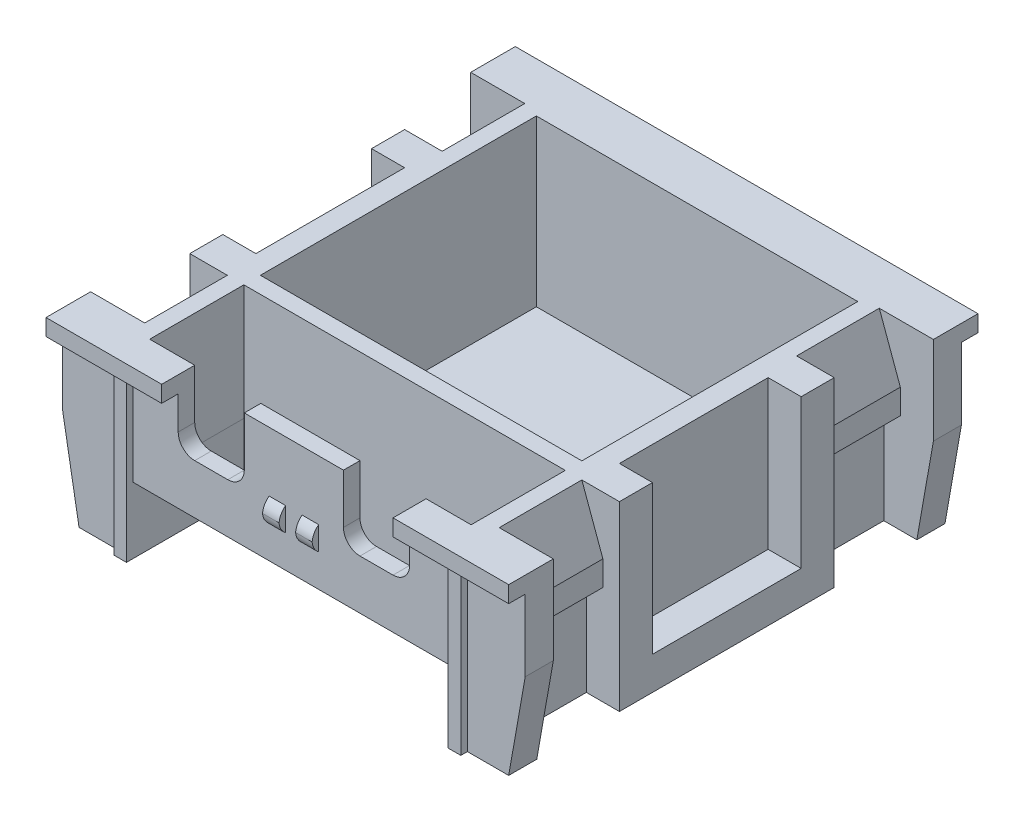
SolidWorks part; units mm, degrees
ref_plane "Front Plane" through (0, 0, 0) normal (0, 0, 1) x (1, 0, 0)
ref_plane "Top Plane" through (0, 0, 0) normal (0, 1, 0) x (1, 0, 0)
ref_plane "Right Plane" through (0, 0, 0) normal (1, 0, 0) x (0, 0, -1)
sketch "Sketch1" plane through (0, 0, 0) normal (0, 1, 0) x (1, 0, 0)
  line L1 (-14, 14.2) -> (0, 14.2)
  line L2 (-14, 14.2) -> (-14, 0)
  line L3 (-14, 0) -> (0, 0)
  line L4 (0, 14.2) -> (0, 0)
  dimension "D1" = 14.2
  dimension "D2" = 14
extrude "Boss-Extrude2" add sketch "Sketch1" against normal blind 5.5
sketch "Sketch2" plane through (0, 0, 0) normal (0, 1, 0) x (1, 0, 0)
  line L1 (-14, 12.85) -> (-13, 12.85)
  line L2 (-14, 12.85) -> (-14, 10.35)
  line L3 (-14, 10.35) -> (-13, 10.35)
  line L4 (-13, 12.85) -> (-13, 10.35)
  line L5 (-7, 14.6083) -> (-7, 0.4083)
  line L6 (0, 10.35) -> (-1, 10.35)
  line L7 (-1, 12.85) -> (-1, 10.35)
  line L8 (0, 12.85) -> (0, 10.35)
  line L9 (0, 12.85) -> (-1, 12.85)
  line L10 (0, 3.85) -> (0, 1.35)
  line L11 (-14, 3.85) -> (-13, 3.85)
  line L12 (-14, 3.85) -> (-14, 1.35)
  line L13 (-14, 1.35) -> (-13, 1.35)
  line L14 (-13, 3.85) -> (-13, 1.35)
  line L15 (0, 1.35) -> (-1, 1.35)
  line L16 (-1, 3.85) -> (-1, 1.35)
  line L17 (0, 3.85) -> (-1, 3.85)
  line L18 (-14, 14.2) -> (-14, 0) construction
  line L19 (0, 0) -> (0, 14.2) construction
  line L20 (0, 14.2) -> (-14, 14.2) construction
  line L21 (-14, 0) -> (0, 0) construction
  line M5 (-14, 14.2) -> (-14, 0)
  line M7 (0, 0) -> (0, 14.2)
  dimension "D1" = 0
  dimension "D2" = 0
  dimension "D3" = 1
  dimension "D4" = 1
  dimension "D5" = 0
  dimension "D6" = 1.35
  dimension "D7" = 1.35
  dimension "D8" = 2.5
  dimension "D9" = 2.5
extrude "Cut-Extrude1" cut sketch "Sketch2" against normal blind 2.5 contours L4 L1 L3 M5 | L9 L7 L6 M7 | L14 L11 L13 M5 | L17 L16 L15 M7 region at (-13.5, 0, -2.6) region at (-13.5, 0, -11.6) region at (-0.5, 0, -11.6) region at (-0.5, 0, -2.6)
sketch "Sketch3" plane through (0, -5.5, 0) normal (0, -1, 0) x (1, 0, 0)
  line L0 (-14, -1.35) -> (-12.5, -1.35)
  line L1 (-14, -1.35) -> (-14, -3.85)
  line L2 (-14, -3.85) -> (-12.5, -3.85)
  line L3 (-12.5, -1.35) -> (-12.5, -3.85)
  line L4 (-14, 0) -> (0, 0) construction
  line L5 (-1.5, -3.85) -> (0, -3.85)
  line L6 (0, -1.35) -> (0, -3.85)
  line L7 (-1.5, -1.35) -> (-1.5, -3.85)
  line L8 (-1.5, -1.35) -> (0, -1.35)
  line L9 (0, -10.35) -> (0, -12.85)
  line L10 (-14, -10.35) -> (-12.5, -10.35)
  line L11 (-14, -10.35) -> (-14, -12.85)
  line L12 (-14, -12.85) -> (-12.5, -12.85)
  line L13 (-12.5, -10.35) -> (-12.5, -12.85)
  line L14 (0, -12.85) -> (-1.5, -12.85)
  line L15 (-1.5, -10.35) -> (-1.5, -12.85)
  line L16 (0, -10.35) -> (-1.5, -10.35)
  line L17 (-14, -14.2) -> (-14, 0) construction
  line L18 (0, 0) -> (0, -14.2) construction
  line L19 (0, -14.2) -> (-14, -14.2) construction
  point P8 (-0.75, -12.85)
  dimension "D1" = 0
  dimension "D2" = 0
  dimension "D3" = 2.5
  dimension "D4" = 0
  dimension "D5" = 1.5
  dimension "D6" = 2.5
  dimension "D7" = 2.5
  dimension "D8" = 0
  dimension "D9" = 1.5
  dimension "D10" = 1.35
  dimension "D11" = 2.5
  dimension "D12" = 1.5
  dimension "D13" = 2.5
  dimension "D14" = 1.35
  dimension "D15" = 1.35
  dimension "D16" = 1.35
  dimension "D17" = 1.5
extrude "Cut-Extrude2" cut sketch "Sketch3" against normal blind 3
sketch "Sketch4" plane through (0, 0, 0) normal (0, 1, 0) x (1, 0, 0)
  line L0 (0, 3.85) -> (-1, 3.85) construction
  line L1 (0, 10.35) -> (-0.5, 10.35)
  line L2 (0, 10.35) -> (0, 3.85)
  line L3 (0, 3.85) -> (-0.5, 3.85)
  line L4 (-0.5, 10.35) -> (-0.5, 3.85)
  line L5 (-14, 10.35) -> (-13, 10.35) construction
  line L6 (-13.5, 10.35) -> (-14, 10.35)
  line L7 (-13.5, 10.35) -> (-13.5, 3.85)
  line L8 (-13.5, 3.85) -> (-14, 3.85)
  line L9 (-14, 10.35) -> (-14, 3.85)
extrude "Cut-Extrude3" cut sketch "Sketch4" against normal blind 5.5
sketch "Sketch5" plane through (0, 0, 0) normal (0, 1, 0) x (1, 0, 0)
  line L0 (-13.5, 3.85) -> (-13.5, 10.35) construction
  line L1 (-13.5, 9.35) -> (-12.5, 9.35)
  line L2 (-13.5, 9.35) -> (-13.5, 4.85)
  line L3 (-13.5, 4.85) -> (-12.5, 4.85)
  line L4 (-12.5, 9.35) -> (-12.5, 4.85)
  line L5 (-0.5, 10.35) -> (-0.5, 3.85) construction
  line L6 (-0.5, 9.35) -> (-1.5, 9.35)
  line L7 (-0.5, 9.35) -> (-0.5, 4.85)
  line L8 (-0.5, 4.85) -> (-1.5, 4.85)
  line L9 (-1.5, 9.35) -> (-1.5, 4.85)
  line L10 (-13.5, 10.35) -> (-13, 10.35) construction
  line L11 (-13.5, 3.85) -> (-13, 3.85) construction
  line L12 (-0.5, 10.35) -> (-1, 10.35) construction
  line L13 (-0.5, 3.85) -> (-1, 3.85) construction
  dimension "D1" = 1
  dimension "D2" = 1
  dimension "D3" = 1
  dimension "D4" = 1
  dimension "D5" = 1
  dimension "D6" = 1
extrude "Cut-Extrude4" cut sketch "Sketch5" against normal blind 4.5
chamfer "Chamfer2" distance 1.75 angle 20 2 edges at (-13, 0, -11.6) (-13, 0, -2.6) first distance on face at (-13, -1.25, -11.6) first distance on face at (-13, -1.25, -2.6)
chamfer "Chamfer3" distance 1.75 angle 20 2 edges at (-1, 0, -2.6) (-1, 0, -11.6) first distance on face at (-1, -1.25, -2.6) first distance on face at (-1, -1.25, -11.6)
sketch "Sketch7" plane through (0, 0, 0) normal (0, 1, 0) x (1, 0, 0)
  line L0 (-13.5, 3.85) -> (-12.3631, 3.85) construction
  line L1 (-11.8631, 3.85) -> (-2.1369, 3.85)
  line L2 (-11.8631, 3.85) -> (-11.8631, 1)
  line L3 (-11.8631, 1) -> (-2.1369, 1)
  line L4 (-2.1369, 3.85) -> (-2.1369, 1)
  line L5 (-12.3631, 3.85) -> (-12.3631, 1.35) construction
  line L6 (-1.6369, 1.35) -> (-1.6369, 3.85) construction
  line L7 (-14, 0) -> (0, 0) construction
  dimension "D1" = 0
  dimension "D2" = 0.5
  dimension "D3" = 0.5
  dimension "D4" = 1
  dimension "D5" = 9.7261
extrude "Cut-Extrude5" cut sketch "Sketch7" against normal through all
sketch "Sketch8" plane through (0, 0, 0) normal (0, 1, 0) x (1, 0, 0)
  line L0 (-2.1369, 3.85) -> (-11.8631, 3.85) construction
  line L1 (-11.8631, 4.35) -> (-2.1369, 4.35)
  line L2 (-11.8631, 4.35) -> (-11.8631, 12.7)
  line L3 (-11.8631, 12.7) -> (-2.1369, 12.7)
  line L4 (-2.1369, 4.35) -> (-2.1369, 12.7)
  line L5 (-2.1369, 1) -> (-2.1369, 3.85) construction
  line L6 (0, 14.2) -> (-14, 14.2) construction
  dimension "D1" = 0.5
  dimension "D2" = 0
  dimension "D3" = 1.5
extrude "Cut-Extrude6" cut sketch "Sketch8" against normal blind 5
chamfer "Chamfer4" distance 0.5 angle 80 2 edges at (0, -5.5, -0.675) (0, -5.5, -13.525) first distance on face at (-7, -5.5, -2.425)
chamfer "Chamfer5" distance 0.5 angle 80 2 edges at (-14, -5.5, -13.525) (-14, -5.5, -0.675) first distance on face at (-7, -5.5, -2.425)
sketch "Sketch9" plane through (0, -5.5, 0) normal (0, -1, 0) x (1, 0, 0)
  line L0 (0, 0) -> (0, -1.35) construction
  line L1 (-14, 0) -> (0, 0)
  line L2 (-14, 0) -> (-14, -0.5)
  line L3 (-14, -0.5) -> (0, -0.5)
  line L4 (0, 0) -> (0, -0.5)
  line L5 (-14, -14.2) -> (-14, -12.85) construction
  line L6 (0, -14.2) -> (-14, -14.2)
  line L7 (0, -14.2) -> (0, -13.7)
  line L8 (0, -13.7) -> (-14, -13.7)
  line L9 (-14, -14.2) -> (-14, -13.7)
  dimension "D1" = 0.5
  dimension "D2" = 0.5
extrude "Cut-Extrude7" cut sketch "Sketch9" against normal blind 5
sketch "Sketch11" plane through (0, 0, 0) normal (0, 1, 0) x (1, 0, 0)
  line L0 (-14, 0) -> (0, 0) construction
  line L1 (-10.5, 0) -> (-3.5, 0)
  line L2 (-10.5, 0) -> (-10.5, 0.5)
  line L3 (-10.5, 0.5) -> (-3.5, 0.5)
  line L4 (-3.5, 0) -> (-3.5, 0.5)
  line L5 (-14, 1.35) -> (-14, 0) construction
  line L6 (0, 0) -> (0, 1.35) construction
  line L7 (-11.8631, 1) -> (-2.1369, 1) construction
  line L9 (-3.5, 0.5) -> (-5.5, 0.5)
  line L10 (-3.5, 0.5) -> (-3.5, 1)
  line L11 (-3.5, 1) -> (-5.5, 1)
  line L12 (-5.5, 0.5) -> (-5.5, 1)
  line L13 (-10.5, 0.5) -> (-8.5, 0.5)
  line L14 (-10.5, 0.5) -> (-10.5, 1)
  line L15 (-10.5, 1) -> (-8.5, 1)
  line L16 (-8.5, 0.5) -> (-8.5, 1)
  line M13 (-2.1369, 1) -> (-11.8631, 1)
  line M40 (-14, 0) -> (0, 0)
  dimension "D1" = 3.5
  dimension "D2" = 3.5
  dimension "D3" = 0.5
  dimension "D4" = 2
  dimension "D5" = 2
extrude "Cut-Extrude11" cut sketch "Sketch11" against normal blind 2 contours L3 L16 L14 M13 | L4 L3 L2 M40 | L12 L3 L10 M13 region at (-7, 0, -0.25) region at (-9.5, 0, -0.75) region at (-4.5, 0, -0.75)
fillet "Fillet2" radius 0.5 4 edges at (-8.5, -2, -0.75) (-3.5, -2, -0.75) (-5.5, -2, -0.75) (-10.5, -2, -0.75)
sketch "Sketch12" plane through (0, 0, -0.5) normal (0, 0, 1) x (1, 0, 0)
  line L0 (-13.5, -5.5) -> (-0.5, -5.5) construction
  line L1 (-11.865, -5.5) -> (-2.135, -5.5)
  line L2 (-11.865, -5.5) -> (-11.865, -3.5)
  line L3 (-11.865, -3.5) -> (-2.135, -3.5)
  line L4 (-2.135, -5.5) -> (-2.135, -3.5)
  line L5 (-8.5, 0) -> (-5.5, 0) construction
  point P9 (-7, 0)
  point P10 (-7, -5.5)
  dimension "D1" = 4.865
  dimension "D2" = 9.73
  dimension "D3" = 3.5
  dimension "D4" = 4.865
extrude "Cut-Extrude12" cut sketch "Sketch12" against normal up to vertex (3.35 mm away) up to point (-2.1369, 0, -3.85)
sketch "Sketch13" plane through (0, 0, -0.5) normal (0, 0, 1) x (1, 0, 0)
  line L0 (-3.5, -0.5) -> (0, -0.5) construction
  line L1 (-7.75, -1.8024) -> (-7.25, -1.8024)
  line L2 (-7.75, -1.8024) -> (-7.75, -2.5154)
  line L3 (-7.75, -2.5154) -> (-7.25, -2.5154)
  line L4 (-7.25, -1.8024) -> (-7.25, -2.5154)
  line L5 (-6.75, -1.8024) -> (-6.25, -1.8024)
  line L6 (-6.75, -1.8024) -> (-6.75, -2.5154)
  line L7 (-6.75, -2.5154) -> (-6.25, -2.5154)
  line L8 (-6.25, -1.8024) -> (-6.25, -2.5154)
  line L9 (-2.135, -5.5) -> (-1.75, -5.5)
  line L10 (-2.135, -5.5) -> (-2.135, -0.5)
  line L11 (-2.135, -0.5) -> (-1.75, -0.5)
  line L12 (-1.75, -5.5) -> (-1.75, -0.5)
  line L13 (-10.5, -0.5) -> (-14, -0.5) construction
  line L14 (-11.865, -5.5) -> (-12.25, -5.5)
  line L15 (-11.865, -5.5) -> (-11.865, -0.5)
  line L16 (-11.865, -0.5) -> (-12.25, -0.5)
  line L17 (-12.25, -5.5) -> (-12.25, -0.5)
  line L18 (-5.5, -1.5) -> (-5.5, 0) construction
  line L19 (-8.5, -1.5) -> (-8.5, 0) construction
  dimension "D1" = 0.5
  dimension "D2" = 0.75
  dimension "D3" = 0.75
  dimension "D4" = 0.5
extrude "Boss-Extrude3" add sketch "Sketch13" along normal blind 0.2
fillet "Fillet4" radius 0.5 4 edges at (-7.5, -1.8024, -0.3) (-6.5, -1.8024, -0.3) (-6.5, -2.5154, -0.3) (-7.5, -2.5154, -0.3)
